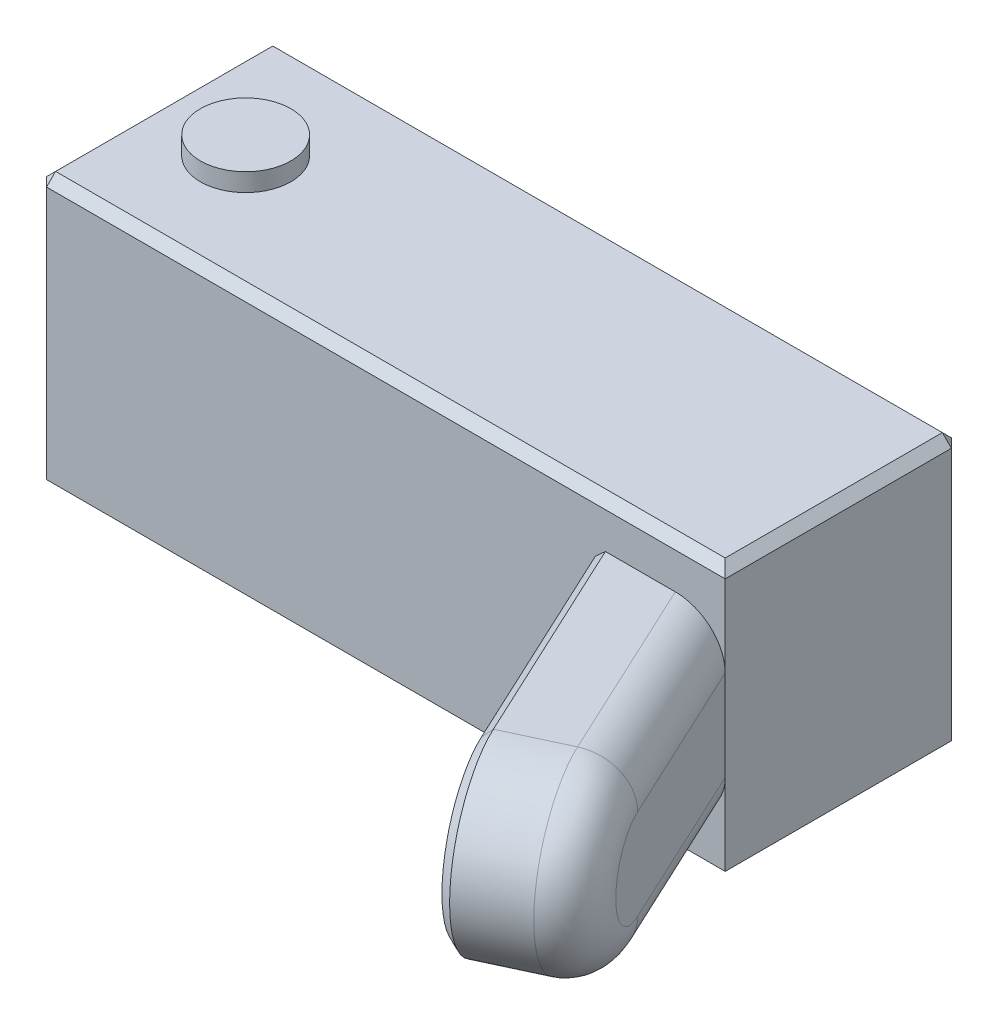
SolidWorks part; units mm, degrees
ref_plane "Front Plane" through (0, 0, 0) normal (0, 0, 1) x (1, 0, 0)
ref_plane "Top Plane" through (0, 0, 0) normal (0, 1, 0) x (1, 0, 0)
ref_plane "Right Plane" through (0, 0, 0) normal (1, 0, 0) x (0, 0, -1)
sketch "Sketch1" plane through (0, 0, 0) normal (0, 1, 0) x (1, 0, 0)
  line L1 (-38, 13) -> (38, 13)
  line L2 (-38, 13) -> (-38, -13)
  line L3 (-38, -13) -> (38, -13)
  line L4 (38, 13) -> (38, -13)
  line L5 (-38, 13) -> (38, -13) construction
  line L6 (-38, -13) -> (38, 13) construction
  point P0 (0, 0)
  dimension "D1" = 26
  dimension "D2" = 76
extrude "Boss-Extrude1" add sketch "Sketch1" along normal blind 15 and the other way blind 15
ref_plane "Plane1" through (26.2337, 0, -12.233) normal (-0.9063, 0, 0.4226) x (0, 1, 0)
sketch "Sketch2" plane through (26.2337, 0, -12.233) normal (-0.9063, 0, 0.4226) x (0, 1, 0)
  line L0 (0, -1000) -> (0, 49000) construction
  line L1 (10, -27.8415) -> (-10, -27.8415)
  line L2 (-15, -27.8415) -> (15, -27.8415) construction
  line L3 (-10, -27.8415) -> (-10, -47.8415)
  line L4 (10, -27.8415) -> (10, -47.8415)
  arc A0 (-10, -47.8415) -> (10, -47.8415) centre (0, -47.8415) ccw
  point P1 (0, -57.8415)
  point P12 (0, -27.8415)
  dimension "D1" = 20
  dimension "D2" = 30
extrude "Boss-Extrude2" add sketch "Sketch2" along normal blind 13 separate body
sketch "Sketch3" plane through (11.7663, 0, 25.233) normal (-0.4226, 0, -0.9063) x (-0.9063, 0, 0.4226)
  line L4 (-28.9457, 10) -> (-28.9457, -10)
  line L5 (-28.9457, -10) -> (-15.9457, -10)
  line L6 (-15.9457, -10) -> (-15.9457, 10)
  line L7 (-15.9457, 10) -> (-28.9457, 10)
  line L8 (-28.9457, 10) -> (-28.9457, -10)
  line L9 (-28.9457, -10) -> (-15.9457, -10)
  line L10 (-15.9457, -10) -> (-15.9457, 10)
  line L11 (-15.9457, 10) -> (-28.9457, 10)
  dimension "D1" = 0
extrude "Boss-Extrude3" add sketch "Sketch3" along normal up to next
fillet "Fillet1" radius 5 3 edges at (42.2262, -10, 22.0631) (42.2262, 10, 22.0631) (50.6785, 0, 40.1892)
chamfer "Chamfer1" distance 1 angle 45 14 edges at (29.1632, -10, 24.8101) (38.8965, 0, 45.6833) (29.1632, 10, 24.8101) (0, -15, -13) (0, -15, 13) (38, -15, 0) (-38, -15, 0) (-38, 0, -13) (-38, 0, 13) (0, 15, 13) (-38, 15, 0) (0, 15, -13) (38, 15, 0) (38, 0, -13)
sketch "Sketch4" plane through (0, 15, 0) normal (0, 1, 0) x (1, 0, 0)
  line L0 (-38, -12) -> (-38, 12) construction
  circle A0 centre (-28, 0) radius 5
  dimension "D1" = 10
  dimension "D2" = 10
extrude "Boss-Extrude4" add sketch "Sketch4" along normal blind 2
